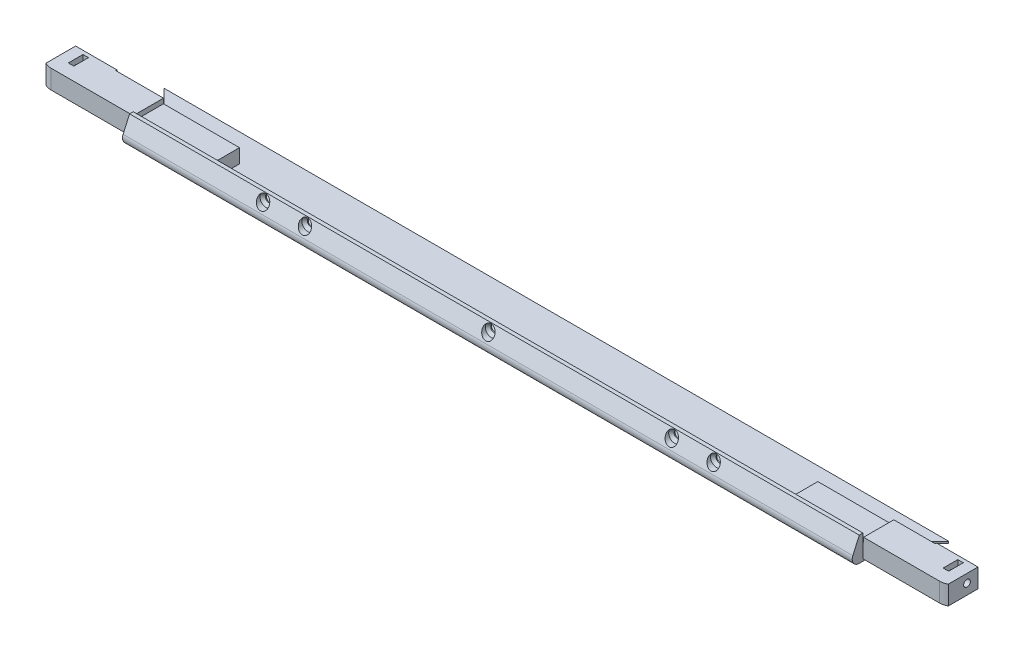
SolidWorks part; units mm, degrees
ref_plane "Front Plane" through (0, 0, 0) normal (0, 0, 1) x (1, 0, 0)
ref_plane "Top Plane" through (0, 0, 0) normal (0, 1, 0) x (1, 0, 0)
ref_plane "Right Plane" through (0, 0, 0) normal (1, 0, 0) x (0, 0, -1)
sketch "Sketch1" plane through (0, 0, 0) normal (0, 1, 0) x (1, 0, 0)
  line L0 (-118.36, 0) -> (120.36, 0)
  line L1 (120.36, 0) -> (120.36, 1.3)
  line L2 (120.36, 1.3) -> (145.3, 1.3)
  line L3 (-118.36, 0) -> (-118.36, 1.3)
  line L4 (-118.36, 1.3) -> (-145.3, 1.3)
  line L5 (147.6, 1.9012) -> (147.6, 11.6)
  line L6 (-151.3, 84.8764) -> (151.3, 84.8764) construction
  line L7 (-151.3, 84.8764) -> (-151.3, 0) construction
  line L8 (-151.3, 0) -> (151.3, 0) construction
  line L9 (151.3, 84.8764) -> (151.3, 0) construction
  line L10 (147.6, 11.6) -> (134.1, 11.6)
  line L11 (134.1, 11.6) -> (134.1, 11.2)
  line L12 (134.1, 11.2) -> (95.6, 11.2)
  line L13 (95.6, 11.2) -> (95.6, 1.2)
  line L14 (95.6, 1.2) -> (-93.6, 1.2)
  line L15 (-147.6, 1.9012) -> (-147.6, 11.6)
  line L16 (-147.6, 11.6) -> (-134.1, 11.6)
  line L17 (-134.1, 11.6) -> (-134.1, 11.2)
  line L18 (-134.1, 11.2) -> (-93.6, 11.2)
  line L19 (-93.6, 11.2) -> (-93.6, 1.2)
  line L20 (120.46, 1.3) -> (120.46, 11.3) construction
  line L21 (120.46, 11.3) -> (129.46, 20.3) construction
  line L22 (129.46, 20.3) -> (129.46, 10.7338) construction
  line L23 (-118.46, 1.3) -> (-118.46, 11.3) construction
  line L24 (-118.46, 11.3) -> (-127.46, 20.3) construction
  line L25 (-127.46, 20.3) -> (-127.46, 28.1252) construction
  arc A0 (145.3, 1.3) -> (147.6, 1.9012) centre (145.3, 6) ccw
  arc A1 (-145.3, 1.3) -> (-147.6, 1.9012) centre (-145.3, 6) cw
  dimension "D6" = 4.7
  dimension "D1" = 1.3
  dimension "D2" = 302.6
  dimension "D3" = 6
  dimension "D4" = 6
  dimension "D5" = 3.7
  dimension "D7" = 11.6
  dimension "D8" = 3.7
  dimension "D9" = 1.2
  dimension "D10" = 10
  dimension "D11" = 189.2
  dimension "D12" = 135
  dimension "D13" = 0.1
  dimension "D14" = 9
  dimension "D15" = 21.84
  dimension "D16" = 0.1
  dimension "D17" = 17.2
  dimension "D18" = 38.5
  dimension "D19" = 17.2
  dimension "D20" = 135
  dimension "D21" = 0.1
  dimension "D22" = 0.1
  dimension "D23" = 9
  dimension "D24" = 23.84
extrude "Boss-Extrude1" add sketch "Sketch1" along normal blind 8
sketch "Sketch2" plane through (0, 0, 0) normal (0, -1, 0) x (1, 0, 0)
  line L0 (120.36, -1.2) -> (120.36, -11.3414)
  line L1 (95.6, -1.2) -> (-93.6, -1.2) construction
  line L2 (120.36, -11.3414) -> (129.3186, -20.3)
  line L3 (129.3186, -20.3) -> (-127.3186, -20.3)
  line L5 (-118.36, -11.3414) -> (-118.36, -1.2)
  line L6 (-118.36, -1.2) -> (120.36, -1.2)
  line L7 (-118.36, -11.3414) -> (-127.3186, -20.3)
  line L8 (-118.46, -11.3) -> (-127.46, -20.3) construction
  line L9 (120.46, -11.3) -> (129.46, -20.3) construction
  line L10 (-127.46, -20.3) -> (-127.3186, -20.3) construction
  dimension "D1" = 0.1
  dimension "D2" = 0.1
extrude "Boss-Extrude2" add sketch "Sketch2" against normal blind 0.6
sketch "Sketch3" plane through (0, 0, 0) normal (0, -1, 0) x (1, 0, 0)
  line L0 (-118.36, -11.2) -> (-134.1, -11.2)
  line L1 (120.36, -1.3) -> (147.6, -1.3)
  line L2 (120.36, -1.3) -> (120.36, -11.2)
  line L4 (147.6, -1.3) -> (147.6, -11.6)
  line L5 (-118.36, -1.3) -> (-147.6, -1.3)
  line L6 (-118.36, -1.3) -> (-118.36, -11.2)
  line L8 (-147.6, -1.3) -> (-147.6, -11.6)
  line L9 (-134.1, -11.2) -> (-134.1, -11.6)
  line L10 (-134.1, -11.6) -> (-147.6, -11.6)
  line L11 (147.6, -11.6) -> (134.1, -11.6)
  line L12 (134.1, -11.6) -> (134.1, -11.2)
  line L13 (134.1, -11.2) -> (120.36, -11.2)
extrude "Cut-Extrude1" cut sketch "Sketch3" against normal up to surface (0.6 mm away) up to face at (1, 0.6, -11.0483)
sketch "Sketch4" plane through (147.6, 0, 0) normal (1, 0, 0) x (0, 0, -1)
  line L0 (8, 4) -> (0, 4) construction
  line L1 (0, 8) -> (0, 0) construction
  line L2 (11.6, 8) -> (11.6, 0.6) construction
  circle A0 centre (8, 4) radius 1.1
  dimension "D1" = 2.2
  dimension "D2" = 3.6
extrude "Cut-Extrude2" cut sketch "Sketch4" against normal up to surface (13.5 mm away) up to face at (134.1, 4.3, -11.4)
sketch "Sketch5" plane through (-147.6, 0, 0) normal (-1, 0, 0) x (0, 0, 1)
  circle A1 centre (-8, 4) radius 1.1
  circle A2 centre (-8, 4) radius 1.1
  dimension "D1" = 0
extrude "Cut-Extrude3" cut sketch "Sketch5" against normal up to surface (13.5 mm away) up to face at (-134.1, 4.3, -11.4)
sketch "Sketch6" plane through (147.6, 0, 0) normal (1, 0, 0) x (0, 0, -1)
  line L0 (11.6, 8) -> (11.6, 0.6) construction
  line L1 (10.4, 5.3856) -> (8, 6.7713) construction
  line L2 (8, 6.7713) -> (5.6, 5.3856) construction
  line L3 (5.6, 5.3856) -> (5.6, 2.6144)
  line L4 (5.6, 2.6144) -> (8, 1.2287)
  line L5 (8, 1.2287) -> (10.4, 2.6144)
  line L6 (10.4, 2.6144) -> (10.4, 5.3856)
  line L7 (10.4, 5.3856) -> (10.4, 8)
  line L8 (10.4, 8) -> (5.6, 8)
  line L9 (5.6, 8) -> (5.6, 5.3856)
  line L10 (1.9012, 8) -> (11.6, 8) construction
  circle A0 centre (8, 4) radius 2.4 construction
  dimension "D1" = 4.8
extrude "Cut-Extrude6" cut sketch "Sketch6" against normal blind 1.8 from offset 3.6 offset against normal yes
sketch "Sketch7" plane through (-147.6, 0, 0) normal (-1, 0, 0) x (0, 0, 1)
  line L5 (-10.4, 8) -> (-10.4, 2.6144)
  line L6 (-5.6, 8) -> (-10.4, 8)
  line L7 (-5.6, 2.6144) -> (-5.6, 8)
  line L8 (-8, 1.2287) -> (-5.6, 2.6144)
  line L9 (-10.4, 2.6144) -> (-8, 1.2287)
  line L10 (-10.4, 8) -> (-10.4, 2.6144)
  line L11 (-5.6, 8) -> (-10.4, 8)
  line L12 (-5.6, 2.6144) -> (-5.6, 8)
  line L13 (-8, 1.2287) -> (-5.6, 2.6144)
  line L14 (-10.4, 2.6144) -> (-8, 1.2287)
  dimension "D1" = 0
extrude "Cut-Extrude7" cut sketch "Sketch7" against normal blind 1.8 from offset 3.6 offset against normal yes
sketch "Sketch8" plane through (0, 8, 0) normal (0, 1, 0) x (1, 0, 0)
  line L0 (-147.6, 11.6) -> (-147.6, 1.9012) construction
  line L1 (147.6, 20.3) -> (-147.6, 20.3)
  line L2 (147.6, 20.3) -> (147.6, 1.2)
  line L3 (147.6, 1.2) -> (-147.6, 1.2)
  line L4 (-147.6, 20.3) -> (-147.6, 1.2)
  line L5 (147.6, 1.9012) -> (147.6, 11.6) construction
  line L6 (-127.3186, 20.3) -> (129.3186, 20.3) construction
  line L7 (-118.36, 0) -> (120.36, 0) construction
  dimension "D1" = 1.2
extrude "Cut-Extrude8" cut sketch "Sketch8" against normal blind 1.2
sketch "Sketch9" plane through (0, 6.8, 0) normal (0, 1, 0) x (1, 0, 0)
  line L0 (-118.36, 1.2) -> (-93.6, 1.2) construction
  line L1 (120.46, 1.2) -> (95.6, 1.2)
  line L2 (120.46, 1.2) -> (120.46, 11.2)
  line L3 (120.46, 11.2) -> (95.6, 11.2)
  line L4 (95.6, 1.2) -> (95.6, 11.2)
  line L5 (-93.6, 11.2) -> (-118.46, 11.2)
  line L6 (-93.6, 11.2) -> (-93.6, 1.2)
  line L7 (-93.6, 1.2) -> (-118.46, 1.2)
  line L8 (-118.46, 11.2) -> (-118.46, 1.2)
  line L9 (-118.36, 1.2) -> (-118.36, 0) construction
  line L10 (120.36, 0) -> (120.36, 1.2) construction
  line L11 (95.6, 1.2) -> (120.36, 1.2) construction
  dimension "D1" = 0.1
  dimension "D2" = 0.1
extrude "Cut-Extrude9" cut sketch "Sketch9" against normal blind 1.6
sketch "Sketch10" plane through (-118.36, 0, 0) normal (-1, 0, 0) x (0, 0, 1)
  line L0 (0, 8) -> (2.1131, 3.2539)
  line L1 (-11.3414, 0) -> (0, 0) construction
  line L2 (0, 8) -> (0, 0) construction
  line L3 (0, 8) -> (0, 0)
  arc A0 (2.1131, 3.2539) -> (0, 0) centre (0, 2.3131) cw
  dimension "D1" = 24
extrude "Boss-Extrude3" add sketch "Sketch10" against normal up to surface (238.72 mm away) up to face at (120.36, 3.1333, -4.3203)
sketch "Sketch11" plane through (0, 0, -1.2) normal (0, 0, -1) x (-1, 0, 0)
  line L0 (-120.36, 8) -> (118.36, 8) construction
  line L1 (-73.7, 5.8) -> (-60, 5.8) construction
  line L2 (-60, 5.8) -> (0, 5.8) construction
  line L3 (0, 5.8) -> (60, 5.8) construction
  line L4 (60, 5.8) -> (73.7, 5.8) construction
  circle A0 centre (73.7, 5.8) radius 1.1
  circle A1 centre (-73.7, 5.8) radius 1.1
  circle A2 centre (60, 5.8) radius 1.1
  circle A3 centre (0, 5.8) radius 1.1
  circle A4 centre (-60, 5.8) radius 1.1
  dimension "D1" = 2.2
  dimension "D2" = 77.6
  dimension "D3" = 77.6
  dimension "D4" = 2.2
  dimension "D5" = 2.2
  dimension "D6" = 60
extrude "Cut-Extrude10" cut sketch "Sketch11" against normal blind 1.2
sketch "Sketch12" plane through (0, 0, 0) normal (0, 0, -1) x (-1, 0, 0)
  circle A0 centre (-73.7, 5.8) radius 2
  circle A1 centre (73.7, 5.8) radius 2
  circle A2 centre (-60, 5.8) radius 2
  circle A3 centre (0, 5.8) radius 2
  circle A4 centre (60, 5.8) radius 2
  dimension "D1" = 4
extrude "Cut-Extrude11" cut sketch "Sketch12" against normal up to next
chamfer "Chamfer1" distance 0.9 angle 45 5 edges at (72.6, 5.8, 0) (-74.8, 5.8, 0) (58.9, 5.8, 0) (-1.1, 5.8, 0) (-61.1, 5.8, 0)
equation "\"LCD_Height\"= 158mm"
equation "\"LCD_Width\"= 268mm"
equation "\"LCD_PCB_Height\"= 10mm"
equation "\"LCD_PCB_Width\"= 189"
equation "\"LCD_PCB_LOff\"= 38.5"
equation "\"LCD_Thick\"= 2.9mm"
equation "\"LCD_TBezel\"= 4.6mm"
equation "\"LCD_LBezel\"= 4.94mm"
equation "\"LCD_RBezel\"= 6.94mm"
equation "\"LCD_BBezel\"= 9.4mm"
equation "\"Wing_Height\"= 11.5mm"
equation "\"Wing_Width\"= 5mm"
equation "\"Wing_Corner\"= 1mm"
equation "\"Wing_Hole_VOff\"= 3.5mm"
equation "\"Wing_Hole_HOff\"= 2.8mm"
equation "\"Wing_Spacing\"= 128.9 + 2 * \"Wing_Hole_VOff\" - \"Wing_Height\""
equation "\"Wing_TOff\"= 8.35 - \"Wing_Hole_VOff\""
equation "\"Wing_DOff\"= 0.7mm"
equation "\"Wing_Thick\"= 0.3mm"
equation "\"Print_Gap\"= 0.2mm"
equation "\"Pin1_Pos\"= 89.75mm"
equation "\"Pin_Space\"= 0.5mm"
equation "\"Pin_num\"= 30"
equation "\"Min_Thick\"= 1.2mm"
equation "\"Nut_Width\"= 4.8mm"
equation "\"Nut_Height\"= 5.6mm"
equation "\"Nut_Thick\"= 1.6mm"
equation "\"Screw_Hole\"= 2.2mm"
equation "\"Screw_Chamf\"= 0.9mm"
equation "\"Bezel_Gap\"= 0.4mm"
equation "\"USB_Width\"= 16mm"
equation "\"Corner_Radius\"= 6mm"
equation "\"D1@Sketch1\"=\"Min_Thick\" + \"Print_Gap\" / 2"
equation "\"D2@Sketch1\"= \"LCD_Width\" + \"Print_Gap\" + 2 * \"USB_Width\" + 2 * \"Min_Thick\""
equation "\"D3@Sketch1\"= \"Corner_Radius\""
equation "\"D4@Sketch1\"=\"Corner_Radius\""
equation "\"D5@Sketch1\"= 3 * \"Min_Thick\" + \"Print_Gap\" / 2"
equation "\"D6@Sketch1\"=\"Corner_Radius\" - \"Print_Gap\" / 2 - \"Min_Thick\""
equation "\"D7@Sketch1\"=\"Corner_Radius\" + \"Screw_Chamf\" + \"Screw_Hole\" / 2 + \"Nut_Width\"/2 + \"Min_Thick\" "
equation "\"D8@Sketch1\"=\"Print_Gap\" / 2 + 3 * \"Min_Thick\""
equation "\"D9@Sketch1\"=\"Min_Thick\""
equation "\"D10@Sketch1\"=\"LCD_PCB_Height\""
equation "\"D11@Sketch1\"=\"LCD_PCB_Width\" + \"Print_Gap\""
equation "\"D13@Sketch1\"=\"Print_Gap\" / 2"
equation "\"D14@Sketch1\"=\"LCD_BBezel\" - \"Bezel_Gap\""
equation "\"D15@Sketch1\"=\"USB_Width\" + \"Min_Thick\" + \"Print_Gap\" / 2 + \"LCD_LBezel\" - \"Bezel_Gap\""
equation "\"D16@Sketch1\"=\"Print_Gap\" / 2"
equation "\"D17@Sketch1\"= \"USB_Width\" + \"Min_Thick\""
equation "\"D19@Sketch1\"=\"USB_Width\" + \"Min_Thick\""
equation "\"D21@Sketch1\"=\"Print_Gap\" / 2"
equation "\"D22@Sketch1\"=\"Print_Gap\" / 2"
equation "\"D23@Sketch1\"=\"LCD_BBezel\" - \"Bezel_Gap\""
equation "\"D24@Sketch1\"=\"USB_Width\" + \"Min_Thick\" + \"Print_Gap\" / 2 +\"LCD_RBezel\" - \"Bezel_Gap\""
equation "\"D1@Sketch2\"=\"Print_Gap\" / 2"
equation "\"D2@Sketch2\"=\"Print_Gap\" / 2"
equation "\"D1@Sketch4\"=\"Screw_Hole\""
equation "\"D2@Sketch4\"=\"Nut_Width\" / 2 + \"Min_Thick\""
equation "\"D1@Sketch6\"=\"Nut_Width\" "
equation "\"D1@Cut-Extrude6\"=\"Nut_Thick\" + \"Print_Gap\""
equation "\"D19@Cut-Extrude6\"=\"Min_Thick\" * 3"
equation "\"D1@Cut-Extrude7\"=\"Nut_Thick\" + \"Print_Gap\""
equation "\"D19@Cut-Extrude7\"=\"Min_Thick\" * 3"
equation "\"D1@Sketch8\"=\"Min_Thick\""
equation "\"D1@Cut-Extrude8\"=\"Min_Thick\""
equation "\"D1@Cut-Extrude9\"=1.6"
equation "\"D1@Sketch9\"=\"Print_Gap\" / 2"
equation "\"Stand_Tilt\"= 8"
equation "\"Screen_Tilt\"= 24"
equation "\"Stand_Splay\"= 16"
equation "\"D1@Sketch10\"=\"Screen_Tilt\""
equation "\"D2@Sketch9\"=\"Print_Gap\" / 2"
equation "\"D1@Sketch11\"=\"Screw_Hole\""
equation "\"D2@Sketch11\"=80 -  \"Nut_Width\" / 2"
equation "\"D3@Sketch11\"=80 - \"Nut_Width\" / 2"
equation "\"D4@Sketch11\"=2.2"
equation "\"D1@Cut-Extrude10\"=\"Min_Thick\""
equation "\"D1@Sketch12\"=\"Screw_Hole\" + 2 * \"Screw_Chamf\""
equation "\"D1@Chamfer1\"=\"Screw_Chamf\""
